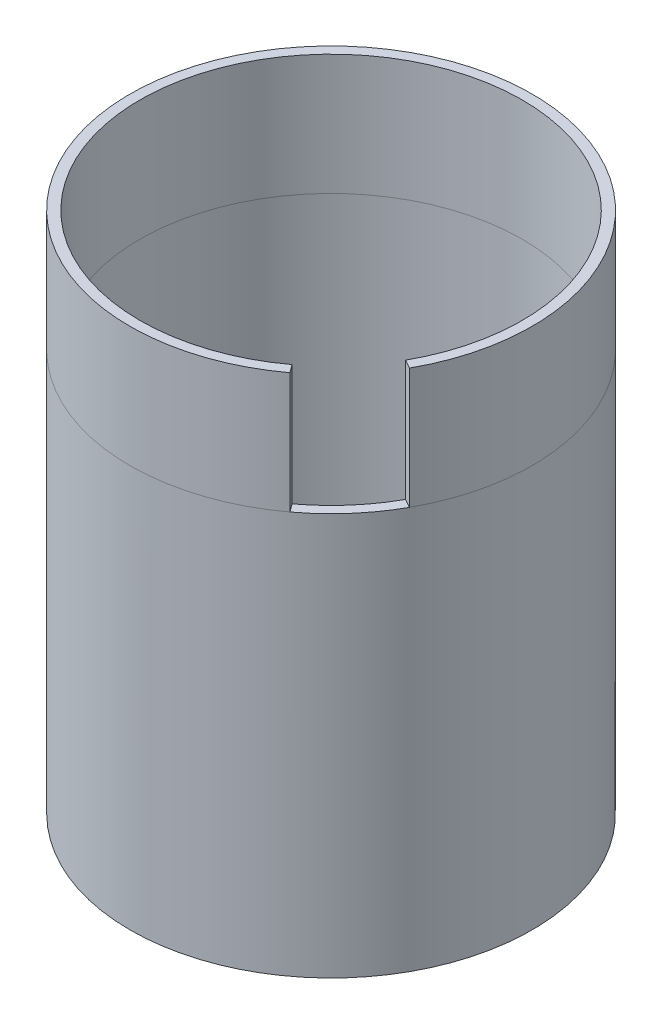
SolidWorks part; units mm, degrees
ref_plane "前基準面" through (0, 0, 0) normal (0, 0, 1) x (1, 0, 0)
ref_plane "上基準面" through (0, 0, 0) normal (0, 1, 0) x (1, 0, 0)
ref_plane "右基準面" through (0, 0, 0) normal (1, 0, 0) x (0, 0, -1)
sketch "草圖1" plane through (0, 0, 0) normal (0, 1, 0) x (1, 0, 0)
  circle A0 centre (0, 0) radius 4.75
  circle A1 centre (0, 0) radius 5
  dimension "D1" = 9.5
  dimension "D2" = 10
extrude "填料-伸長3" add sketch "草圖1" along normal blind 10
sketch "草圖2" plane through (0, 10, 0) normal (0, 1, 0) x (1, 0, 0)
  line L0 (-0.0018, 0.0015) -> (2.8382, -3.8088) construction
  line L1 (2.8382, -3.8088) -> (2.9876, -4.0092)
  line L2 (-0.0018, 0.0015) -> (4.1544, -2.3029) construction
  line L3 (4.1544, -2.3029) -> (4.373, -2.4241)
  arc A1 (2.8382, -3.8088) -> (4.1544, -2.3029) centre (-0.0018, 0.0015) cw
  circle A2 centre (0, 0) radius 4.75 construction
  arc A3 (4.373, -2.4241) -> (2.9876, -4.0092) centre (-0.0018, 0.0015) ccw
  circle A4 centre (0, 0) radius 5 construction
  point P8 (3.8363, -3.2067)
  dimension "D1" = 2
extrude "填料-伸長5" add sketch "草圖2" along normal blind 3
